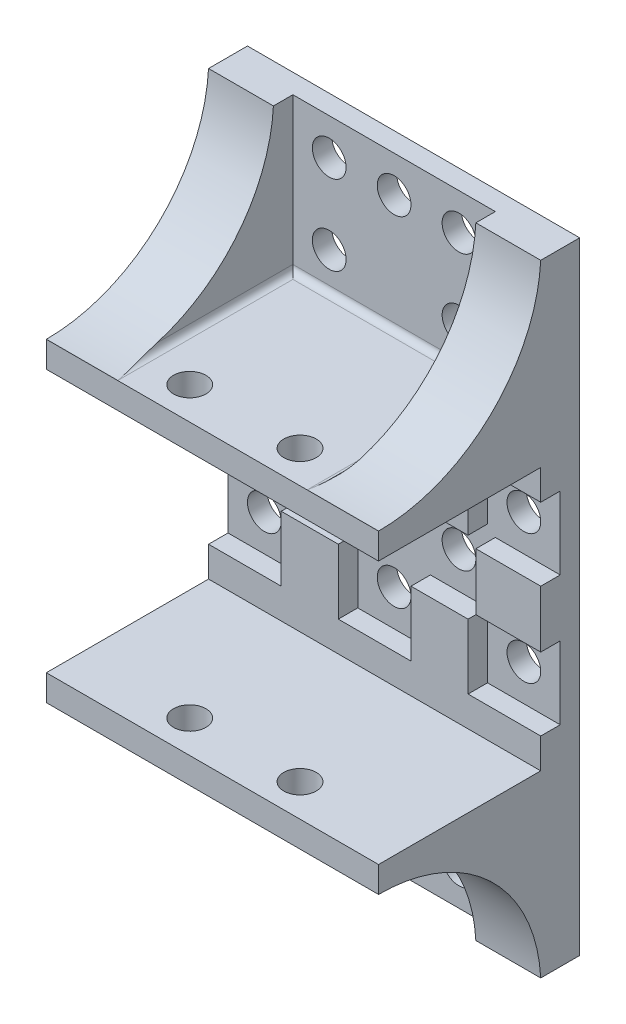
SolidWorks part; units mm, degrees
material "ABS"
ref_plane "Front Plane" through (0, 0, 0) normal (0, 0, 1) x (1, 0, 0)
ref_plane "Top Plane" through (0, 0, 0) normal (0, 1, 0) x (1, 0, 0)
ref_plane "Right Plane" through (0, 0, 0) normal (1, 0, 0) x (0, 0, -1)
sketch "Sketch1" plane through (0, 0, 0) normal (0, 0, 1) x (1, 0, 0)
  line L1 (0, 0) -> (100, 0)
  line L2 (0, 0) -> (0, 120)
  line L3 (0, 120) -> (100, 120)
  line L4 (100, 0) -> (100, 120)
  dimension "D1" = 120
  dimension "D2" = 100
extrude "Boss-Extrude1" [suppressed] add sketch "Sketch1" along normal blind 1.5
sketch "Sketch2" [suppressed] plane through (0, 0, 0) normal (0, 0, -1) x (-1, 0, 0)
  line L0 (-82.275, 100) -> (-17.725, 100) construction
  line L1 (-17.725, 100) -> (-17.725, 20) construction
  line L2 (-17.725, 20) -> (-82.275, 20) construction
  line L3 (-82.275, 20) -> (-82.275, 100) construction
  line L4 (-82.275, 100) -> (-100, 100) construction
  line L5 (-100, 0) -> (-100, 120) construction
  line L6 (-82.275, 100) -> (-82.275, 120) construction
  line L7 (-100, 120) -> (0, 120) construction
  line L8 (-17.725, 100) -> (-17.725, 120) construction
  line L9 (-17.725, 100) -> (0, 100) construction
  line L10 (0, 120) -> (0, 0) construction
  line L11 (-17.725, 20) -> (0, 20) construction
  line L12 (-17.725, 20) -> (-17.725, 0) construction
  line L13 (0, 0) -> (-100, 0) construction
  line L14 (-82.275, 20) -> (-82.275, 0) construction
  line L15 (-82.275, 20) -> (-100, 20) construction
  circle A0 centre (-82.275, 20) radius 2.5
  circle A1 centre (-17.725, 20) radius 2.5
  circle A2 centre (-17.725, 100) radius 2.5
  circle A3 centre (-82.275, 100) radius 2.5
  dimension "D1" = 5
  dimension "D2" = 17.725
  dimension "D3" = 20
extrude "Cut-Extrude1" [suppressed] cut sketch "Sketch2" against normal blind 1.5
sketch "Sketch4" [suppressed] plane through (0, 0, 1.5) normal (0, 0, 1) x (1, 0, 0)
  line L0 (50, 120) -> (50, 0) construction
  line L1 (0, 0) -> (100, 0)
  line L2 (0, 0) -> (0, 120)
  line L3 (0, 120) -> (100, 120)
  line L4 (100, 0) -> (100, 120)
  line L5 (50, 60) -> (50, 70) construction
  line L6 (50, 60) -> (50, 50) construction
  line L7 (0, 60) -> (100, 60) construction
  line L8 (40, 60) -> (50, 60) construction
  line L9 (50, 60) -> (60, 60) construction
  circle A0 centre (50, 70) radius 2.65
  circle A1 centre (50, 50) radius 2.65
  circle A2 centre (40, 60) radius 2.65
  circle A3 centre (60, 60) radius 2.65
  point P15 (50, 60)
  dimension "D2" = 5.3
  dimension "D3" = 5.3
  dimension "D1" = 20
extrude "Cut-Extrude2" [suppressed] cut sketch "Sketch4" against normal up to surface (1.5 mm away) contours A1 | A0 | A2 | A3
sketch "Sketch5" [suppressed] plane through (0, 0, 0) normal (0, 0, 1) x (1, 0, 0)
  line L0 (90, 120) -> (10.1259, 120)
  line L1 (99.8961, 8.0521) -> (99.8961, 111.438)
  line L2 (10, 0) -> (91.314, 0)
  line L3 (0, 110.1259) -> (0, 10)
  line L4 (3.0179, 117.1601) -> (96.9011, 2.6447) construction
  line L5 (0, 120) -> (100, 0) construction
  line L6 (100, 0) -> (100, 120) construction
  circle A0 centre (50, 17.7) radius 2.6
  circle A1 centre (17.7, 17.7) radius 3.55
  circle A2 centre (75.25, 17.7) radius 2.6
  circle A3 centre (40, 17.7) radius 2.6
  circle A4 centre (60, 90) radius 2.6
  circle A5 centre (40, 90) radius 2.6
  circle A6 centre (60, 102.3) radius 2.6
  circle A7 centre (10, 50) radius 2.6
  circle A8 centre (70, 50) radius 2.6
  circle A9 centre (90, 70) radius 2.6
  circle A10 centre (30, 70) radius 2.6
  circle A11 centre (10, 70) radius 2.6
  circle A12 centre (17.7, 102.3) radius 3.55
  circle A13 centre (60, 30) radius 2.6
  circle A14 centre (85.25, 60) radius 2.6
  circle A15 centre (40, 60) radius 2.6
  circle A16 centre (60, 40) radius 2.6
  circle A17 centre (50, 102.3) radius 2.6
  circle A18 centre (50, 60) radius 2.6
  circle A19 centre (50, 70) radius 2.6
  circle A20 centre (50, 50) radius 2.6
  circle A21 centre (60, 60) radius 2.6
  circle A22 centre (17.7, 60) radius 3.55
  circle A23 centre (85.25, 102.3) radius 2.6
  circle A24 centre (40, 40) radius 2.6
  circle A25 centre (27.7, 102.3) radius 3.55
  circle A26 centre (40, 30) radius 2.6
  circle A27 centre (70, 70) radius 2.6
  circle A28 centre (90, 50) radius 2.6
  circle A29 centre (30, 50) radius 2.6
  circle A30 centre (75.25, 102.3) radius 2.6
  circle A31 centre (40, 102.3) radius 2.6
  circle A32 centre (40, 80) radius 2.6
  circle A33 centre (60, 80) radius 2.6
  circle A34 centre (60, 17.7) radius 2.6
  circle A35 centre (27.7, 17.7) radius 3.55
  circle A36 centre (85.25, 17.7) radius 2.6
  arc A37 (10.1259, 120) -> (0, 110.1259) centre (10, 110) ccw
  arc A38 (99.8961, 111.438) -> (90, 120) centre (90, 110) ccw
  arc A39 (91.314, 0) -> (99.8961, 8.0521) centre (90, 10) ccw
  arc A40 (0, 10) -> (10, 0) centre (10, 10) ccw
extrude "Cut-Extrude4" [suppressed] cut sketch "Sketch5" along normal up to surface (1.5 mm away) contours A35 | A3 | A0 | A34 | A2 | A13 | A26 | A24 | A16 | A8 | A28 | A22 | A7 | A29 | A18 | A14 | A9 | A27 | A32 | A10 | A11 | A33 | A4 | A5 | A17 | A6 | A30 | A25 | A31
sketch "Sketch6" plane through (0, 0, 0) normal (0, 0, 1) x (1, 0, 0)
  line L0 (90, 120) -> (10.1259, 120)
  line L1 (99.8961, 8.0521) -> (99.8961, 111.438)
  line L2 (10, 0) -> (91.314, 0)
  line L3 (0, 110.1259) -> (0, 10)
  line L4 (3.0179, 117.1601) -> (96.9011, 2.6447) construction
  line L5 (0, 120) -> (100, 0) construction
  circle A0 centre (50, 17.7) radius 2.6
  circle A1 centre (17.7, 17.7) radius 3.55
  circle A2 centre (75.25, 17.7) radius 2.6
  circle A3 centre (40, 17.7) radius 2.6
  circle A4 centre (60, 90) radius 2.6
  circle A5 centre (40, 90) radius 2.6
  circle A6 centre (60, 102.3) radius 2.6
  circle A7 centre (10, 50) radius 2.6
  circle A8 centre (70, 50) radius 2.6
  circle A9 centre (90, 70) radius 2.6
  circle A10 centre (30, 70) radius 2.6
  circle A11 centre (10, 70) radius 2.6
  circle A12 centre (17.7, 102.3) radius 3.55
  circle A13 centre (60, 30) radius 2.6
  circle A14 centre (85.25, 60) radius 2.6
  circle A15 centre (40, 60) radius 2.6
  circle A16 centre (60, 40) radius 2.6
  circle A17 centre (50, 102.3) radius 2.6
  circle A18 centre (50, 60) radius 2.6
  circle A19 centre (50, 70) radius 2.6
  circle A20 centre (50, 50) radius 2.6
  circle A21 centre (60, 60) radius 2.6
  circle A22 centre (17.7, 60) radius 3.55
  circle A23 centre (85.25, 102.3) radius 2.6
  circle A24 centre (40, 40) radius 2.6
  circle A25 centre (27.7, 102.3) radius 3.55
  circle A26 centre (40, 30) radius 2.6
  circle A27 centre (70, 70) radius 2.6
  circle A28 centre (90, 50) radius 2.6
  circle A29 centre (30, 50) radius 2.6
  circle A30 centre (75.25, 102.3) radius 2.6
  circle A31 centre (40, 102.3) radius 2.6
  circle A32 centre (40, 80) radius 2.6
  circle A33 centre (60, 80) radius 2.6
  circle A34 centre (60, 17.7) radius 2.6
  circle A35 centre (27.7, 17.7) radius 3.55
  circle A36 centre (85.25, 17.7) radius 2.6
  arc A37 (10.1259, 120) -> (0, 110.1259) centre (10, 110) ccw
  arc A38 (99.8961, 111.438) -> (90, 120) centre (90, 110) ccw
  arc A39 (91.314, 0) -> (99.8961, 8.0521) centre (90, 10) ccw
  arc A40 (0, 10) -> (10, 0) centre (10, 10) ccw
extrude "Boss-Extrude2" [suppressed] add sketch "Sketch6" along normal blind 1.5
sketch "Sketch7" plane through (0, 0, 0) normal (0, 0, 1) x (1, 0, 0)
  line L0 (25.6, 20.25) -> (-25.6, -20.25) construction
  line L1 (25.6, -20.25) -> (-25.6, -20.25)
  line L2 (25.6, -20.25) -> (25.6, 20.25)
  line L3 (25.6, 20.25) -> (-25.6, 20.25)
  line L4 (-25.6, -20.25) -> (-25.6, 20.25)
  line L5 (-25.6, -20.25) -> (-25.6, -47.9)
  line L6 (-25.6, -47.9) -> (25.6, -47.9)
  line L7 (25.6, -47.9) -> (25.6, -20.25)
  line L8 (25.6, 0) -> (-25.6, 0) construction
  line L9 (25.6, 47.9) -> (25.6, 20.25)
  line L10 (-25.6, 20.25) -> (-25.6, 47.9)
  line L11 (-25.6, 47.9) -> (25.6, 47.9)
  line L12 (-25.6, 15.6) -> (-14.4, 15.6)
  line L13 (-14.4, 15.6) -> (-14.4, 4.4)
  line L14 (-14.4, 4.4) -> (-25.6, 4.4)
  line L15 (-20, 7.4) -> (-20, 4.4)
  line L16 (-17.4, 10) -> (-14.4, 10) construction
  line L17 (-15.6, 0) -> (-12.6, 0) construction
  line L18 (-15.6, -4.4) -> (-15.6, 4.4)
  line L19 (-10, 2.6) -> (-10, 5.6) construction
  line L20 (-10, 5.6) -> (-14.4, 5.6)
  line L21 (-10, 5.6) -> (-5.6, 5.6)
  line L22 (-5.6, 5.6) -> (-5.6, 15.6)
  line L23 (-5.6, 10) -> (-2.6, 10) construction
  line L24 (0, 12.6) -> (0, 15.6) construction
  line L25 (5.6, 15.6) -> (-5.6, 15.6)
  line L26 (25.6, 15.6) -> (14.4, 15.6)
  line L27 (14.4, 15.6) -> (14.4, 4.4)
  line L28 (14.4, 4.4) -> (25.6, 4.4)
  line L29 (15.6, -4.4) -> (15.6, 4.4)
  line L30 (10, 5.6) -> (14.4, 5.6)
  line L31 (10, 5.6) -> (5.6, 5.6)
  line L32 (5.6, 5.6) -> (5.6, 15.6)
  line L33 (-10, -5.6) -> (-14.4, -5.6)
  line L34 (-25.6, -15.6) -> (-14.4, -15.6)
  line L35 (-14.4, -4.4) -> (-25.6, -4.4)
  line L36 (-14.4, -15.6) -> (-14.4, -4.4)
  line L37 (-10, -5.6) -> (-5.6, -5.6)
  line L38 (-5.6, -5.6) -> (-5.6, -15.6)
  line L39 (5.6, -15.6) -> (-5.6, -15.6)
  line L40 (5.6, -5.6) -> (5.6, -15.6)
  line L41 (10, -5.6) -> (5.6, -5.6)
  line L42 (10, -5.6) -> (14.4, -5.6)
  line L43 (25.6, -15.6) -> (14.4, -15.6)
  line L44 (14.4, -15.6) -> (14.4, -4.4)
  line L45 (14.4, -4.4) -> (25.6, -4.4)
  line L46 (-15.6, -47.9) -> (-15.6, -20.25)
  line L47 (15.6, -47.9) -> (15.6, -20.25)
  line L48 (-15.6, 47.9) -> (-15.6, 20.25)
  line L49 (15.6, 47.9) -> (15.6, 20.25)
  line L50 (-25.6, 24.25) -> (25.6, 24.25)
  line L51 (-25.6, -24.25) -> (25.6, -24.25)
  circle A0 centre (0, -42.3) radius 2.6
  circle A3 centre (-10, -42.3) radius 2.6
  circle A4 centre (10, 30) radius 2.6
  circle A5 centre (-10, 30) radius 2.6
  circle A6 centre (10, 42.3) radius 2.6
  circle A8 centre (20, -10) radius 2.6
  circle A10 centre (-20, 10) radius 2.6
  circle A13 centre (10, -30) radius 2.6
  circle A15 centre (-10, 0) radius 2.6
  circle A16 centre (10, -20) radius 2.6 construction
  circle A17 centre (0, 42.3) radius 2.6
  circle A18 centre (0, 0) radius 2.6
  circle A19 centre (0, 10) radius 2.6
  circle A20 centre (0, -10) radius 2.6
  circle A21 centre (10, 0) radius 2.6
  circle A24 centre (-10, -20) radius 2.6 construction
  circle A26 centre (-10, -30) radius 2.6
  circle A27 centre (20, 10) radius 2.6
  circle A29 centre (-20, -10) radius 2.6
  circle A31 centre (-10, 42.3) radius 2.6
  circle A32 centre (-10, 20) radius 2.6 construction
  circle A33 centre (10, 20) radius 2.6 construction
  circle A34 centre (10, -42.3) radius 2.6
  point P6 (0, 0)
  point P7 (-22.6, -10)
  point P106 (15.6, 0)
  point P107 (-10, -44.9)
  point P110 (-12.6, -42.3)
  dimension "D1" = 40.5
  dimension "D2" = 3
  dimension "D3" = 3
  dimension "D4" = 3
  dimension "D5" = 3
  dimension "D6" = 4
extrude "Boss-Extrude3" add sketch "Sketch7" against normal blind 6 contours L11 L10 L3 L9 A31 A17 A6 A5 A4 | L4 L1 L2 L3 A29 A27 A21 A20 A19 A18 A15 A10 A8 | L6 L7 L1 L5 A34 A26 A13 A3 A0 | L32 L31 L30 L27 L26 L2 L3 L4 L12 L13 L20 L21 L22 L25 | A10 L14 L13 L12 L4 | L27 L28 L2 L26 A27 | L29 L45 L2 L28 | L45 L44 L43 L2 A8 | L43 L44 L42 L41 L40 L39 L38 L37 L33 L36 L34 L4 L1 L2 | L35 L18 L14 L4 | L34 L36 L35 L4 A29 | L6 L46 L1 L5 | L47 L6 L7 L1 | L11 L49 L3 L9 | L48 L11 L10 L3 | L50 L49 L3 L9 | L47 L51 L7 L1 | L50 L48 L3 L49 | L50 L10 L3 L48 | L5 L51 L46 L1 | L46 L51 L47 L1 region at (20.6, -22.25, 0) region at (20.6, -19.7175, 0) region at (0, -22.25, 0) region at (20, -15.4416, 0) region at (20.6, -36.075, 0) region at (-20.6, -22.25, 0) region at (0, -35.8556, 0) region at (20.6, 0, 0) region at (-20.6, -36.075, 0) region at (20.6, 4.5584, 0) region at (15, -3.9588, 0) region at (-25.4416, -10, 0) region at (20, 16.1325, 0) region at (-20.6, 0, 0) region at (20.6, 22.25, 0) region at (-25.4416, 10, 0) region at (0, 22.25, 0) region at (20.6, 36.075, 0) region at (-20.6, 22.25, 0) region at (0, 35.8556, 0) region at (-20.6, 36.075, 0)
extrude "Cut-Extrude5" cut sketch "Sketch7<6>" against normal blind 3 contours L49 L11 L48 L3 A31 A17 A6 A5 A4 | L27 L28 L2 L26 A27 | L44 L45 L29 L28 L27 L30 L31 L32 L25 L22 L21 L20 L13 L14 L18 L35 L36 L33 L37 L38 L39 L40 L41 L42 A21 A20 A19 A18 A15 | L45 L44 L43 L2 A8 | L34 L36 L35 L4 A29 | A10 L14 L13 L12 L4 | L6 L47 L1 L46 A34 A26 A13 A3 A0 region at (20, -15.4416, 0) region at (0, -35.8556, 0) region at (20.6, 4.5584, 0) region at (15, -3.9588, 0) region at (-25.4416, -10, 0) region at (-25.4416, 10, 0) region at (0, 35.8556, 0)
sketch "Sketch7<6>" plane through (0, 0, 0) normal (0, 0, 1) x (1, 0, 0) same geometry as "Sketch7"
extrude "Boss-Extrude4" add sketch "Sketch7<9>" along normal blind 25 contours L5 L51 L46 L1 | L46 L51 L47 L1 | L47 L51 L7 L1 | L50 L49 L3 L9 | L50 L48 L3 L49 | L50 L10 L3 L48 region at (20.6, -22.25, 0) region at (0, -22.25, 0) region at (-20.6, -22.25, 0) region at (20.6, 22.25, 0) region at (0, 22.25, 0) region at (-20.6, 22.25, 0)
sketch "Sketch7<9>" plane through (0, 0, 0) normal (0, 0, 1) x (1, 0, 0) same geometry as "Sketch7"
sketch "Sketch9" plane through (0, -24.25, 0) normal (0, -1, 0) x (1, 0, 0)
  line L0 (0, 20) -> (-25.6, 20) construction
  line L4 (0, 20) -> (0, 25) construction
  line L5 (-25.6, 25) -> (25.6, 25) construction
  line L6 (-25.6, 25) -> (-25.6, 0) construction
  line L8 (25.6, 0) -> (-25.6, 0) construction
  circle A0 centre (-8.5, 20) radius 2.5
  circle A1 centre (8.5, 20) radius 2.5
  dimension "D2" = 5
  dimension "D1" = 20
  dimension "D3" = 17
fillet "Fillet1" radius 25 4 edges at (20.6, -24.25, 0) (-20.6, -24.25, 0) (-20.6, 24.25, 0) (20.6, 24.25, 0)
fillet "Fillet2" radius 1 6 edges at (-15.6, -24.25, 10.9818) (15.6, -24.25, 10.9818) (15.6, 24.25, 10.9818) (-15.6, 24.25, 10.9818) (0, 24.25, -3) (0, -24.25, -3)
extrude "Cut-Extrude6" cut sketch "Sketch9" against normal up to surface (48.5 mm away) up to face at (0, 24.25, 18.2318)
